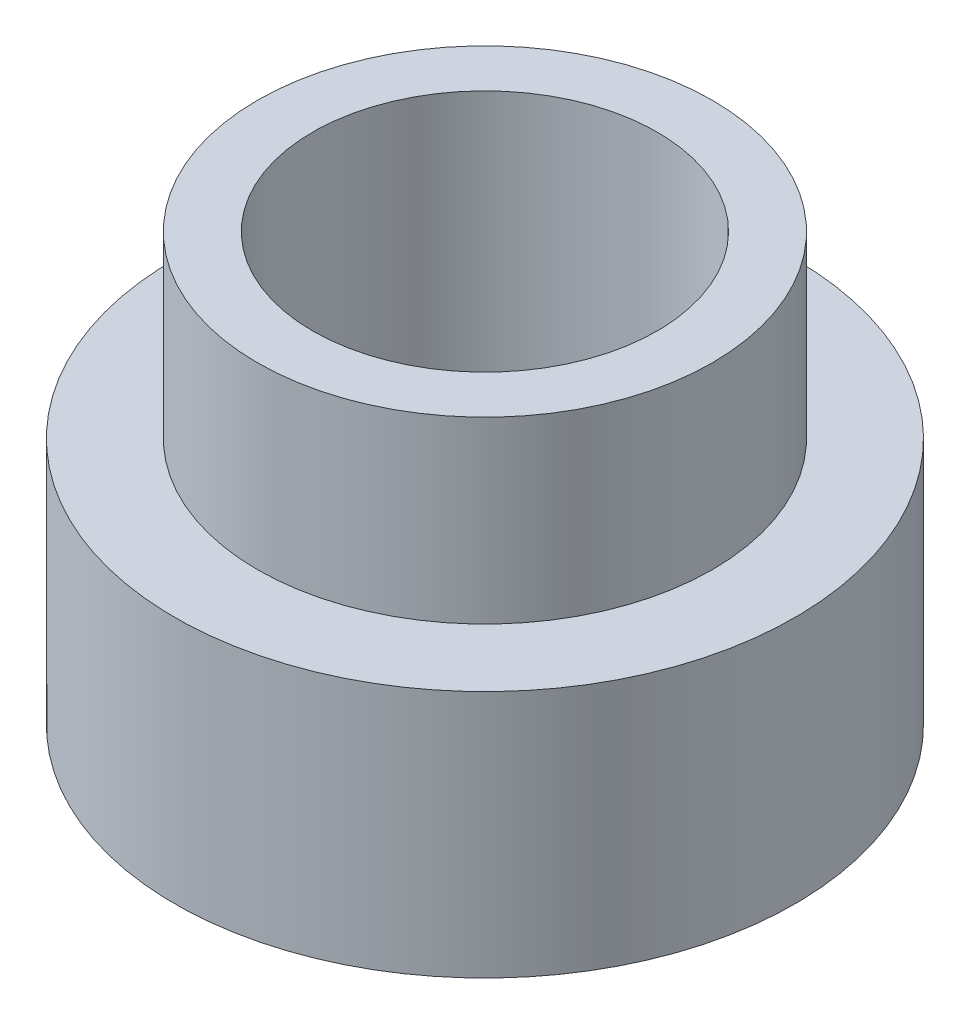
SolidWorks part; units mm, degrees
ref_plane "Front Plane" through (0, 0, 0) normal (0, 0, 1) x (1, 0, 0)
ref_plane "Top Plane" through (0, 0, 0) normal (0, 1, 0) x (1, 0, 0)
ref_plane "Right Plane" through (0, 0, 0) normal (1, 0, 0) x (0, 0, -1)
sketch "Sketch1" plane through (0, 0, 0) normal (0, 1, 0) x (1, 0, 0)
  circle A0 centre (0, 0) radius 2.25
  dimension "D1" = 4.5
extrude "Boss-Extrude1" add sketch "Sketch1" along normal blind 3.1
sketch "Sketch2" plane through (0, 3.1, 0) normal (0, 1, 0) x (1, 0, 0)
  circle A0 centre (0, 0) radius 1.65
  dimension "D1" = 3.3
extrude "Cut-Extrude1" cut sketch "Sketch2" against normal blind 1.3 flip side to cut
sketch "Sketch3" plane through (0, 3.1, 0) normal (0, 1, 0) x (1, 0, 0)
  circle A0 centre (0, 0) radius 1.25
  dimension "D1" = 2.5
extrude "Cut-Extrude2" cut sketch "Sketch3" against normal through all
